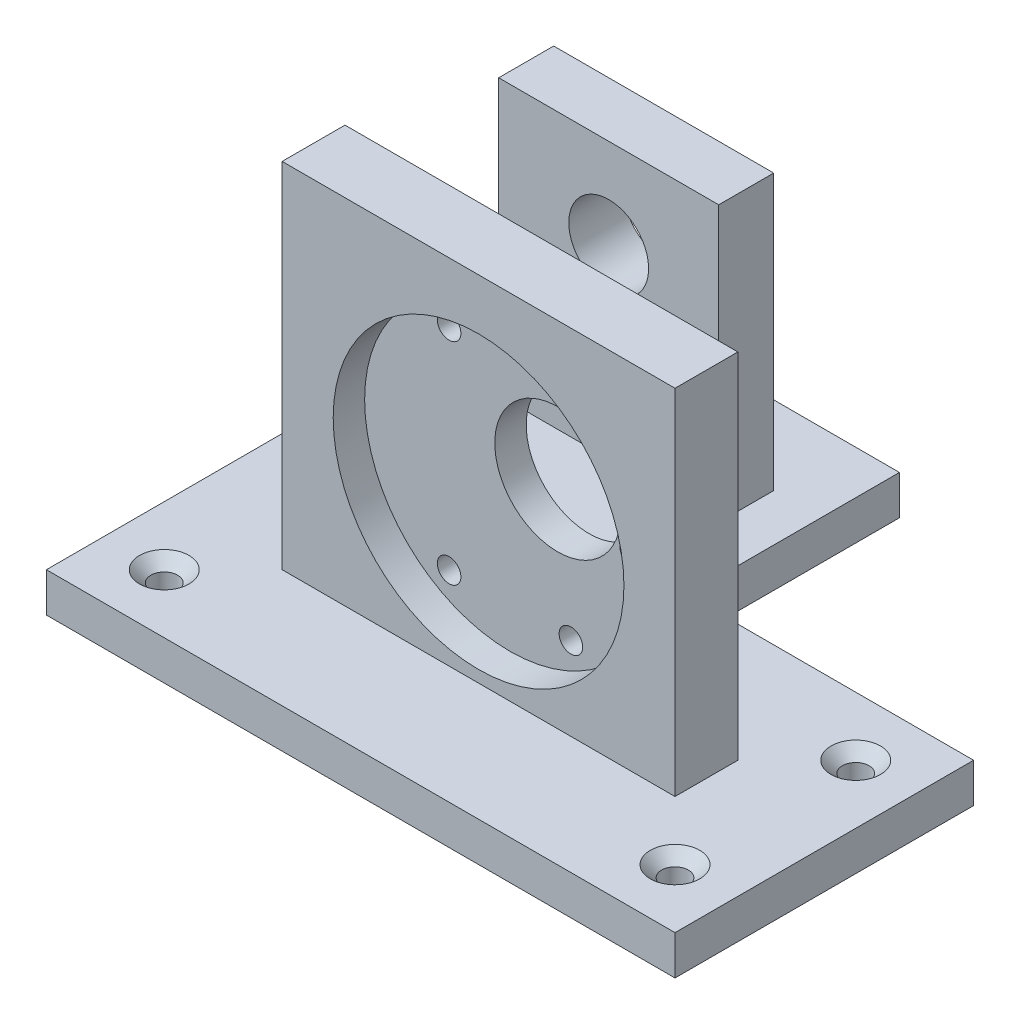
SolidWorks part; units mm, degrees
other "Markup1"
sketch "Sketch5" plane through (25, 50, 8) normal (0.9645, 0.1424, 0.2224) x (0.1697, 0.3107, -0.9352)
ref_plane "Front Plane" through (0, 0, 0) normal (0, 0, 1) x (1, 0, 0)
ref_plane "Top Plane" through (0, 0, 0) normal (0, 1, 0) x (1, 0, 0)
ref_plane "Right Plane" through (0, 0, 0) normal (1, 0, 0) x (0, 0, -1)
sketch "Sketch3" plane through (0, 0, 0) normal (0, 0, 1) x (1, 0, 0)
  line L1 (-25, 50) -> (25, 50)
  line L2 (-25, 50) -> (-25, 0)
  line L3 (-25, 0) -> (25, 0)
  line L4 (25, 50) -> (25, 0)
  line L5 (-7.75, 38.4234) -> (7.75, 38.4234) construction
  line L6 (7.75, 38.4234) -> (15.5, 25) construction
  line L7 (15.5, 25) -> (7.75, 11.5766) construction
  line L8 (7.75, 11.5766) -> (-7.75, 11.5766) construction
  line L9 (-7.75, 11.5766) -> (-15.5, 25) construction
  line L10 (-15.5, 25) -> (-7.75, 38.4234) construction
  line L12 (-20.1843, 13.3466) -> (22.8058, 38.167) construction
  circle A5 centre (-7.75, 38.4234) radius 1.5
  circle A6 centre (7.75, 38.4234) radius 1.5
  circle A8 centre (-7.75, 11.5766) radius 1.5
  circle A9 centre (7.75, 11.5766) radius 1.5
  circle A10 centre (15.5, 25) radius 1.5
  circle A11 centre (6.0622, 28.5) radius 8
  point P4 (0, 0)
  point P27 (-11.625, 18.2883)
  point P28 (11.625, 31.7117)
  dimension "D4" = 25
  dimension "D9" = 16
  dimension "D3" = 3
  dimension "D1" = 50
  dimension "D2" = 50
  dimension "D6" = 120
  dimension "D7" = 120
  dimension "D8" = 15.5
  dimension "D10" = 6.4234
extrude "Boss-Extrude1" add sketch "Sketch3" along normal blind 8 contours L2 L3 L4 L1
extrude "Cut-Extrude2" cut sketch "Sketch3<3>" along normal blind 10 contours A6 | A5 | A8 | A9 | A10 | A11
sketch "Sketch3<3>" plane through (0, 0, 0) normal (0, 0, 1) x (1, 0, 0) same geometry as "Sketch3"
sketch "Sketch4" plane through (0, 0, 8) normal (0, 0, 1) x (1, 0, 0)
  line L0 (-15.5, 25) -> (15.5, 25) construction
  circle A0 centre (0, 25) radius 18.5
  dimension "D1" = 37
extrude "Cut-Extrude3" cut sketch "Sketch4" against normal blind 4 contours A0
sketch "Sketch6" plane through (0, 0, 8) normal (0, 0, 1) x (1, 0, 0)
  line L1 (-40, 5) -> (40, 5)
  line L2 (-40, 5) -> (-40, 0)
  line L3 (-40, 0) -> (40, 0)
  line L4 (40, 5) -> (40, 0)
  point P4 (0, 0)
  dimension "D1" = 80
  dimension "D2" = 5
extrude "Boss-Extrude2" add sketch "Sketch6" against normal blind 23 and the other way blind 15
sketch "Sketch7" plane through (0, 5, 0) normal (0, 1, 0) x (1, 0, 0)
  line L0 (-40, -23) -> (-40, 15) construction
  line L1 (-40, -23) -> (-32.5, -23)
  line L2 (-40, -23) -> (-40, -15.5)
  line L3 (-40, -15.5) -> (-32.5, -15.5)
  line L4 (-32.5, -23) -> (-32.5, -15.5)
  line L5 (-40, -4) -> (40, -4) construction
  line L6 (40, -23) -> (40, 15) construction
  line L7 (0, 15) -> (0, -23) construction
  line L8 (40, 15) -> (-40, 15) construction
  line L9 (40, -23) -> (-40, -23) construction
  point P18 (-32.5, 7.5)
  point P20 (32.5, -15.5)
  point P21 (32.5, 7.5)
  dimension "D1" = 7.5
hole_wizard "CSK for M3 Flat Head Machine Screw1" positions "Sketch8" profile "Sketch9" countersink size "M3" standard "ANSI Metric" end condition through all
sketch "Sketch8" plane through (0, 5, 0) normal (0, 1, 0) x (1, 0, 0)
  point P0 (-32.5, 7.5)
  point P3 (-32.5, -15.5)
  point P6 (32.5, -15.5)
  point P9 (32.5, 7.5)
sketch "Sketch9" plane through (-32.5, 5, -7.5) normal (1, 0, 0) x (0, 0, 1)
  line L0 (0, 0) -> (0, 5)
  line L1 (0, 5) -> (1.7, 5)
  line L2 (1.7, 5) -> (1.7, 1.45)
  line L3 (1.7, 1.45) -> (3.15, 0)
  line L5 (3.15, 0) -> (0, 0)
  line L6 (-1.7, 1.45) -> (-3.15, 0) construction
  line L11 (0, -6.35) -> (0, 107.95) construction
  dimension "Thru Hole Dia." = 3.4
  dimension "Thru Hole Depth" = 5
  dimension "Near C'Sink Dia." = 6.3
  dimension "Near C'Sink Angle" = 90
sketch "Sketch11" plane through (0, 0, 0) normal (0, 0, -1) x (-1, 0, 0)
  line L0 (-40, 5) -> (40, 5) construction
  line L2 (-6.0622, 28.5) -> (16.4378, 28.5) construction
  circle A0 centre (16.4378, 28.5) radius 5.08
  circle A1 centre (16.4378, 28.5) radius 6.08
  dimension "D2" = 10.16
  dimension "D3" = 12.16
  dimension "D1" = 22.5
extrude "Boss-Extrude3" add sketch "Sketch11" along normal blind 5
sketch "Sketch12" plane through (0, 0, -15) normal (0, 0, -1) x (-1, 0, 0)
  line L0 (-40, 5) -> (40, 5) construction
  line L2 (-3.5622, 5) -> (-3.5622, 0)
  line L4 (36.4378, 5) -> (36.4378, 0)
  line L5 (2.4378, 5) -> (30.4378, 5)
  line L6 (-3.5622, 0) -> (36.4378, 0)
  line L8 (2.4378, 5) -> (2.4378, 40)
  line L14 (30.4378, 40) -> (30.4378, 5)
  line L15 (-3.5622, 5) -> (2.4378, 5)
  line L17 (30.4378, 5) -> (36.4378, 5)
  line L19 (2.4378, 40) -> (30.4378, 40)
  line L20 (16.4378, 40.4148) -> (16.4378, 28.5) construction
  circle A0 centre (16.4378, 28.5) radius 5.08
  circle A1 centre (16.4378, 28.5) radius 6.08 construction
  point P7 (16.4378, 40)
  line M13 (40, 5) -> (-40, 5)
  line M15 (-40, 0) -> (40, 0)
  dimension "D4" = 10.16
  dimension "D1" = 35
  dimension "D2" = 40
  dimension "D3" = 6
  dimension "D5" = 5
extrude "Boss-Extrude4" add sketch "Sketch12" along normal blind 10 contours L20 L5 L2 M13 M15 | L20 L6 L4 M13 region at (-16.4378, 2.5, -15)
sketch "Sketch13" plane through (0, 0, -25) normal (0, 0, -1) x (-1, 0, 0)
  line L0 (2.4378, 5) -> (30.4378, 5)
  line L1 (2.4378, 5) -> (2.4378, 40)
  line L2 (30.4378, 40) -> (30.4378, 5)
  line L3 (2.4378, 40) -> (30.4378, 40)
  line L4 (36.4378, 5) -> (-3.5622, 5) construction
  circle A1 centre (16.4378, 28.5) radius 5.08
  point P0 (16.4378, 5)
  point P8 (16.4378, 5)
  dimension "D3" = 10.16
  dimension "D1" = 35
  dimension "D2" = 28
extrude "Boss-Extrude5" add sketch "Sketch13" along normal blind 7 separate body contours A1 | L1 L3 L2 L0
sketch "Sketch14" plane through (0, 0, -25) normal (0, 0, -1) x (-1, 0, 0)
  line L0 (-3.5622, 5) -> (-3.5622, 0) construction
  line L1 (-3.5622, 5) -> (36.4378, 5)
  line L2 (-3.5622, 5) -> (-3.5622, 0)
  line L3 (-3.5622, 0) -> (36.4378, 0)
  line L4 (36.4378, 5) -> (36.4378, 0)
  line L5 (36.4378, 5) -> (-3.5622, 5) construction
extrude "Boss-Extrude6" add sketch "Sketch14" along normal blind 17
